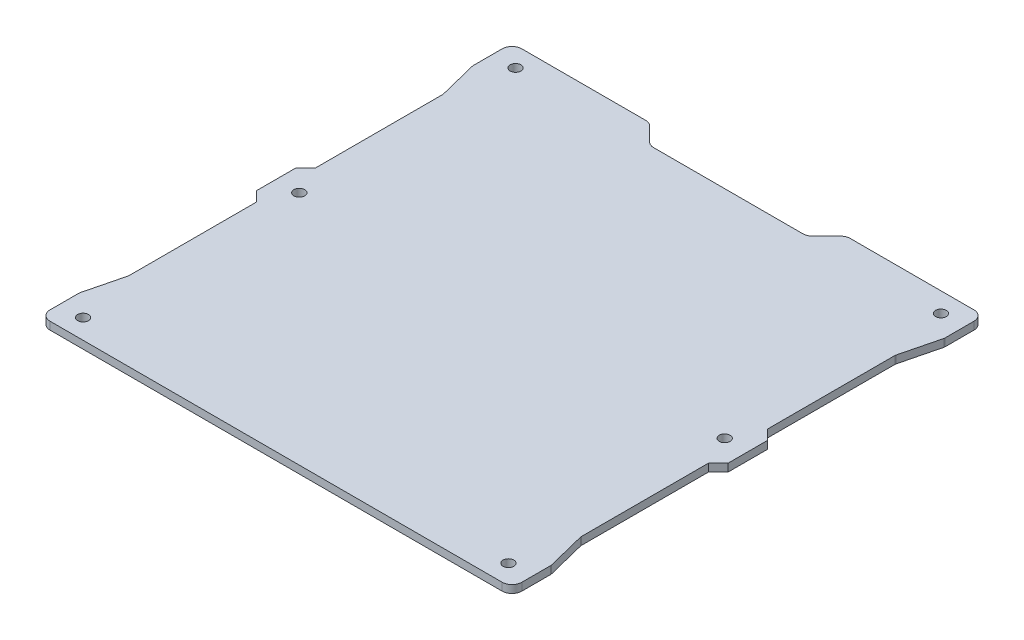
SolidWorks part; units mm, degrees
ref_plane "Front Plane" through (0, 0, 0) normal (0, 0, 1) x (1, 0, 0)
ref_plane "Top Plane" through (0, 0, 0) normal (0, 1, 0) x (1, 0, 0)
ref_plane "Right Plane" through (0, 0, 0) normal (1, 0, 0) x (0, 0, -1)
sketch "Sketch1" plane through (0, 0, 0) normal (0, 1, 0) x (1, 0, 0)
  line L0 (-50.8, 139.7) -> (50.8, 139.7)
  line L2 (-127, 152.4) -> (-127, -152.4)
  line L3 (-127, -152.4) -> (127, -152.4)
  line L4 (127, 152.4) -> (127, -152.4)
  line L5 (-127, 152.4) -> (127, -152.4) construction
  line L6 (-127, -152.4) -> (127, 152.4) construction
  line L8 (-50.8, 139.7) -> (-63.5, 152.4)
  line L9 (50.8, 139.7) -> (63.5, 152.4)
  line L10 (-63.5, 152.4) -> (-127, 152.4)
  line L11 (63.5, 152.4) -> (127, 152.4)
  line L12 (-63.5, 152.4) -> (63.5, 152.4)
  point P0 (0, 0)
  point P6 (0, 152.4)
  point P9 (0, 139.7)
  dimension "D1" = 254
  dimension "D3" = 127
  dimension "D4" = 101.6
  dimension "D5" = 12.7
  dimension "D2" = 304.8
extrude "Boss-Extrude1" add sketch "Sketch1" along normal mid plane 5 contours L11 L9 L0 L8 L10 L2 L3 L4 region at (0, 0, 2.7953)
sketch "Sketch2" plane through (0, 0, 0) normal (0, 1, 0) x (1, 0, 0)
  line L0 (0, 0) -> (0, 139.7) construction
  line L1 (-50.8, 139.7) -> (50.8, 139.7) construction
  line L2 (0, 139.7) -> (-127, 0) construction
  line L3 (-127, 152.4) -> (-127, -152.4) construction
  line L4 (-127, 0) -> (0, 0) construction
  line L5 (-127, -152.4) -> (127, -152.4) construction
  line L6 (63.5, 152.4) -> (127, 152.4) construction
  line L7 (152.4, 152.4) -> (152.4, -152.4) construction
  line L8 (127, 152.4) -> (127, -152.4) construction
  line L9 (127, 152.4) -> (152.4, 152.4)
  line L10 (152.4, 152.4) -> (152.4, 127)
  line L11 (152.4, 127) -> (146.05, 101.6)
  line L12 (146.05, 101.6) -> (146.05, -101.6)
  line L13 (127, 152.4) -> (127, -152.4)
  line L15 (127, -152.4) -> (152.4, -152.4)
  line L16 (152.4, -152.4) -> (152.4, -127)
  line L17 (152.4, -127) -> (146.05, -101.6)
  line L18 (-127, 152.4) -> (-152.4, 152.4)
  line L19 (-152.4, 152.4) -> (-152.4, 127)
  line L20 (-152.4, 127) -> (-146.05, 101.6)
  line L21 (-146.05, 101.6) -> (-146.05, -101.6)
  line L22 (-152.4, -127) -> (-146.05, -101.6)
  line L23 (-152.4, -152.4) -> (-152.4, -127)
  line L24 (-127, -152.4) -> (-152.4, -152.4)
  line L25 (-127, 152.4) -> (-127, -152.4)
  circle A0 centre (137.4, 139.7) radius 3.5
  circle A1 centre (137.4, -139.7) radius 3.5
  circle A2 centre (-137.4, -139.7) radius 3.5
  circle A3 centre (-137.4, 139.7) radius 3.5
  point P39 (-146.05, -152.4)
  point P40 (146.05, 103.4326)
  dimension "D1" = 7
  dimension "D3" = 12.7
  dimension "D2" = 12.7
  dimension "D4" = 25.4
  dimension "D5" = 30
  dimension "D6" = 25.4
  dimension "D7" = 6.35
  dimension "D8" = 25.4
extrude "Boss-Extrude2" add sketch "Sketch2" along normal mid plane 5
fillet "Fillet1" radius 6.35 4 edges at (152.4, 0, 152.4) (-152.4, 0, 152.4) (152.4, 0, -152.4) (-152.4, 0, -152.4)
fillet "Fillet2" radius 6.35 4 edges at (63.5, 0, -152.4) (50.8, 0, -139.7) (-50.8, 0, -139.7) (-63.5, 0, -152.4)
fillet "Fillet3" radius 3 8 edges at (152.4, 0, -127) (146.05, 0, -101.6) (146.05, 0, 101.6) (152.4, 0, 127) (-152.4, 0, 127) (-146.05, 0, 101.6) (-146.05, 0, -101.6) (-152.4, 0, -127)
sketch "Sketch3" plane through (0, 2.5, 0) normal (0, 1, 0) x (1, 0, 0)
  line L0 (0, 0) -> (-137.4, 0) construction
  line L1 (-152.4, 12.7) -> (-152.4, -12.7)
  line L2 (-152.4, 12.7) -> (-146.05, 19.05)
  line L3 (-146.05, 101.2307) -> (-146.05, -101.2307) construction
  line L4 (-152.4, -12.7) -> (-146.05, -19.05)
  line L7 (-152.4, 146.05) -> (-152.4, 127.3693) construction
  line L8 (-146.05, 19.05) -> (-146.05, -19.05)
  line L9 (0, -2.75) -> (0, 2.75) construction
  line L10 (152.4, 12.7) -> (146.05, 19.05)
  line L11 (152.4, 12.7) -> (152.4, -12.7)
  line L12 (152.4, -12.7) -> (146.05, -19.05)
  line L13 (146.05, 19.05) -> (146.05, -19.05)
  circle A0 centre (-137.4, 139.7) radius 3.5 construction
  circle A1 centre (-137.4, 139.7) radius 3.5 construction
  circle A2 centre (-137.4, 0) radius 3.5
  circle A3 centre (137.4, 0) radius 3.5
  point P10 (-152.4, 0)
  line M24 (-146.05, 101.2307) -> (-146.05, -101.2307)
  line M36 (146.05, -101.2307) -> (146.05, 101.2307)
  dimension "D1" = 25.4
  dimension "D2" = 45
extrude "Boss-Extrude3" add sketch "Sketch3" against normal up to surface (5 mm away) contours L1 L4 L2 M24 | L12 L11 L10 M36 region at (-149.0133, 2.5, 0) region at (149.0133, 2.5, 0) up to face at (0, -2.5, -36.5125)
extrude "Cut-Extrude1" cut sketch "Sketch3<4>" against normal up to next contours A2 | A3
sketch "Sketch3<4>" plane through (0, 2.5, 0) normal (0, 1, 0) x (1, 0, 0) same geometry as "Sketch3"
equation "\"Width\" = 10in"
equation "\"Height\" = 12in"
equation "\"CutoutDepth\" = .5in"
equation "\"CutoutWidthHigh\" = 5in"
equation "\"CutoutWidthLow\"= 4in"
equation "\"D3@Sketch1\"=\"CutoutWidthHigh\""
equation "\"D4@Sketch1\"=\"CutoutWidthLow\""
equation "\"D5@Sketch1\"=\"CutoutDepth\""
equation "\"D2@Sketch1\"=\"Height\""
equation "\"D1@Sketch1\"=\"Width\""
